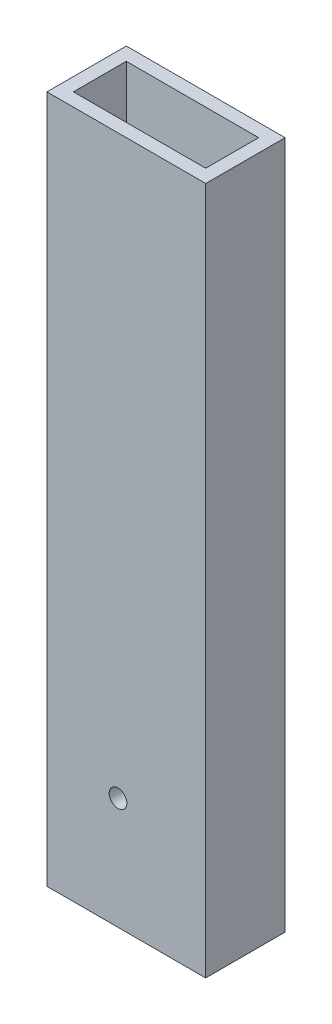
SolidWorks part; units mm, degrees
ref_plane "Front Plane" through (0, 0, 0) normal (0, 0, 1) x (1, 0, 0)
ref_plane "Top Plane" through (0, 0, 0) normal (0, 1, 0) x (1, 0, 0)
ref_plane "Right Plane" through (0, 0, 0) normal (1, 0, 0) x (0, 0, -1)
sketch "Sketch1" plane through (0, 0, 0) normal (0, 1, 0) x (1, 0, 0)
  line L0 (3.175, 15.875) -> (34.925, 15.875)
  line L1 (0, 0) -> (38.1, 0)
  line L2 (0, 0) -> (0, 19.05)
  line L3 (0, 19.05) -> (38.1, 19.05)
  line L4 (38.1, 0) -> (38.1, 19.05)
  line L5 (34.925, 3.175) -> (34.925, 15.875)
  line L6 (3.175, 3.175) -> (34.925, 3.175)
  line L7 (3.175, 3.175) -> (3.175, 15.875)
  dimension "D1" = 38.1
  dimension "D2" = 19.05
extrude "Boss-Extrude1" add sketch "Sketch1" along normal blind 165.1
sketch "Sketch2" plane through (0, 0, -19.05) normal (0, 0, -1) x (-1, 0, 0)
  circle A1 centre (-17.0622, 26.8327) radius 2.125
extrude "Cut-Extrude1" cut sketch "Sketch2" against normal through all
